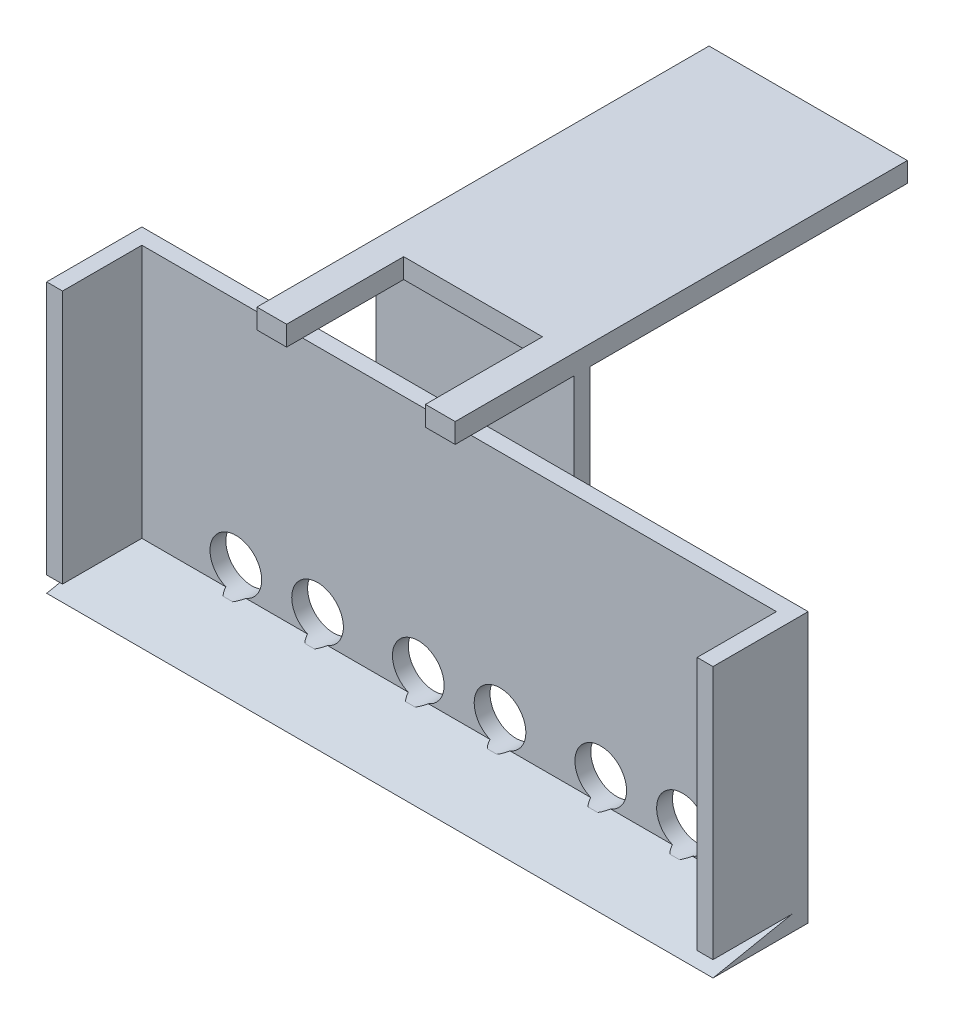
SolidWorks part; units mm, degrees
material "ABS"
ref_plane "Front Plane" through (0, 0, 0) normal (0, 0, 1) x (1, 0, 0)
ref_plane "Top Plane" through (0, 0, 0) normal (0, 1, 0) x (1, 0, 0)
ref_plane "Right Plane" through (0, 0, 0) normal (1, 0, 0) x (0, 0, -1)
sketch "Sketch1" plane through (0, 0, 0) normal (0, 1, 0) x (1, 0, 0)
  line L1 (-101.6, -12.7) -> (101.6, -12.7)
  line L2 (-101.6, -12.7) -> (-101.6, 12.7)
  line L3 (-101.6, 12.7) -> (101.6, 12.7)
  line L4 (101.6, -12.7) -> (101.6, 12.7)
  line L5 (-101.6, -12.7) -> (101.6, 12.7) construction
  line L6 (-101.6, 12.7) -> (101.6, -12.7) construction
  point P0 (0, 0)
  dimension "D1" = 203.2
extrude "Boss-Extrude1" add sketch "Sketch1" along normal blind 5.08 contours L3 L4 L1 L2
ref_plane "Plane1" through (0, 0, 0) normal (1, 0, 0) x (0, 0, -1)
ref_plane "Plane2" through (101.6, 0, 0) normal (1, 0, 0) x (0, 0, -1)
sketch "Sketch4" plane through (101.6, 0, 0) normal (1, 0, 0) x (0, 0, -1)
  line L0 (-12.7, 0) -> (-12.7, 5.08)
  line L1 (-12.7, 5.08) -> (-12.7, 86.36)
  line L2 (-12.7, 86.36) -> (12.7, 86.36)
  line L3 (12.7, 86.36) -> (12.7, 5.08)
  line L4 (12.7, 5.08) -> (12.7, 0)
  line L5 (12.7, 0) -> (-12.7, 0)
extrude "Boss-Extrude2" add sketch "Sketch4" along normal blind 5.08
mirror "Mirror1" about plane through (0, 0, 0) normal (1, 0, 0) of "Boss-Extrude2"
sketch "Sketch5" plane through (0, 0, -12.7) normal (0, 0, -1) x (-1, 0, 0)
  line L1 (-106.68, 86.36) -> (106.68, 86.36)
  line L2 (-106.68, 86.36) -> (-106.68, 0)
  line L3 (-106.68, 0) -> (106.68, 0)
  line L4 (106.68, 86.36) -> (106.68, 0)
extrude "Boss-Extrude3" add sketch "Sketch5" along normal blind 5.08
sketch "Sketch6" plane through (106.68, 0, 0) normal (1, 0, 0) x (0, 0, -1)
  line L0 (-12.7, 0) -> (12.7, 5.08)
  line L4 (12.7, 5.08) -> (-12.7, 5.08)
  line L5 (-12.7, 86.36) -> (-12.7, 0) construction
  line L6 (-12.7, 5.08) -> (-12.7, 0)
  line L7 (-12.7, 0) -> (17.78, 0) construction
  line L8 (17.78, 86.36) -> (17.78, 0) construction
  line L9 (-12.7, 5.08) -> (12.7, 5.08) construction
  dimension "D1" = 5.08
extrude "Cut-Extrude2" cut sketch "Sketch6" against normal through all contours L4 L6 L0
sketch "Sketch7" plane through (0, 0, -17.78) normal (0, 0, -1) x (-1, 0, 0)
  line L0 (-31.75, 50.8) -> (31.75, 50.8)
  line L1 (-106.68, 0) -> (106.68, 0) construction
  line L2 (-31.75, 50.8) -> (-31.75, 114.3)
  line L3 (-31.75, 114.3) -> (31.75, 114.3)
  line L4 (31.75, 114.3) -> (31.75, 50.8)
  point P3 (0, 50.8)
  dimension "D1" = 50.8
  dimension "D2" = 63.5
extrude "Boss-Extrude4" add sketch "Sketch7" along normal blind 5.08 contours L2 L3 L4 L0
sketch "Sketch8" plane through (0, 114.3, 0) normal (0, 1, 0) x (1, 0, 0)
  line L0 (-31.75, 22.86) -> (-31.75, 124.46)
  line L1 (-31.75, 22.86) -> (-31.75, 17.78)
  line L2 (-31.75, 17.78) -> (-31.75, -20.32)
  line L3 (-31.75, -20.32) -> (31.75, -20.32)
  line L4 (31.75, -20.32) -> (31.75, 17.78)
  line L5 (31.75, 17.78) -> (31.75, 22.86)
  line L6 (31.75, 22.86) -> (31.75, 124.46)
  line L7 (31.75, 124.46) -> (-31.75, 124.46)
  dimension "D1" = 101.6
extrude "Boss-Extrude5" add sketch "Sketch8" along normal blind 6.35
sketch "Sketch9" plane through (0, 120.65, 0) normal (0, 1, 0) x (1, 0, 0)
  line L1 (22.225, -41.1636) -> (-22.225, -41.1636)
  line L2 (22.225, -41.1636) -> (22.225, 17.1614)
  line L3 (22.225, 17.1614) -> (-22.225, 17.1614)
  line L4 (-22.225, -41.1636) -> (-22.225, 17.1614)
  point P0 (0, 0)
extrude "Cut-Extrude3" cut sketch "Sketch9" against normal up to next contours L3 L4 L1 L2
sketch "Sketch10" plane through (0, 0, -12.7) normal (0, 0, 1) x (1, 0, 0)
  line L0 (-13.081, 12.7) -> (13.081, 12.7) construction
  line L1 (-106.68, 0) -> (106.68, 0) construction
  circle A0 centre (-13.081, 12.7) radius 8.2697
  circle A1 centre (13.081, 12.7) radius 8.2697
  circle A2 centre (-71.501, 12.7) radius 8.2697
  circle A3 centre (-45.339, 12.7) radius 8.2697
  circle A4 centre (45.339, 12.7) radius 8.2697
  circle A5 centre (71.501, 12.7) radius 8.2697
  point P3 (0, 12.7)
  dimension "D2" = 2
  dimension "D1" = 12.7
  dimension "D3" = 2
extrude "Cut-Extrude4" cut sketch "Sketch10" against normal through all and the other way blind 2.54
